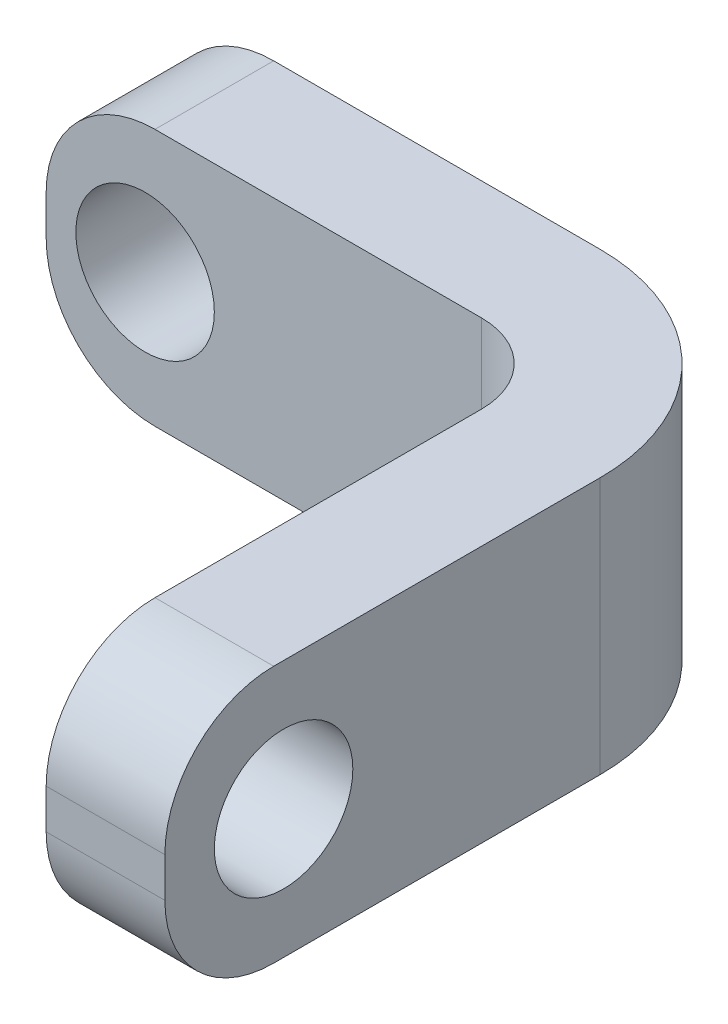
SolidWorks part; units mm, degrees
ref_plane "Plan de face" through (0, 0, 0) normal (0, 0, 1) x (1, 0, 0)
ref_plane "Plan de dessus" through (0, 0, 0) normal (0, 1, 0) x (1, 0, 0)
ref_plane "Plan de droite" through (0, 0, 0) normal (1, 0, 0) x (0, 0, -1)
sketch "Esquisse1" plane through (0, 0, 0) normal (0, 0, 1) x (1, 0, 0)
  line L0 (5, 3.25) -> (5, -3.25)
  line L1 (-8, 3.25) -> (8, 3.25)
  line L2 (-8, 3.25) -> (-8, -3.25)
  line L3 (-8, -3.25) -> (8, -3.25)
  line L4 (8, 3.25) -> (8, -3.25)
  circle A0 centre (-5.5, 0) radius 1.75
  point P4 (0, 3.25)
  point P6 (-8, 0)
  dimension "D1" = 3.5
  dimension "D2" = 2.5
  dimension "D3" = 16
  dimension "D4" = 6.5
  dimension "D5" = 3
extrude "Boss.-Extru.1" add sketch "Esquisse1" along normal blind 3 contours L2 L3 L0 L1 A0 region at (-0.986, 0, 0)
extrude "Boss.-Extru.2" add sketch "Esquisse1<3>" along normal blind 16 contours L4 L1 L0 L3 region at (6.5, 0, 0)
sketch "Esquisse1<3>" plane through (0, 0, 0) normal (0, 0, 1) x (1, 0, 0) same geometry as "Esquisse1"
sketch "Esquisse2" plane through (8, 0, 0) normal (1, 0, 0) x (0, 0, -1)
  line L0 (0, 3.25) -> (0, -3.25) construction
  circle A0 centre (-13, 0) radius 1.75
  dimension "D1" = 3.5
  dimension "D2" = 13
extrude "Enlèv. mat.-Extru.1" cut sketch "Esquisse2" against normal up to next
fillet "Congé1" radius 2.75 4 edges at (6.5, -3.25, 16) (6.5, 3.25, 16) (-8, -3.25, 1.5) (-8, 3.25, 1.5)
fillet "Congé2" radius 2 1 edges at (5, 0, 3)
fillet "Congé3" radius 5 1 edges at (8, 0, 0)
